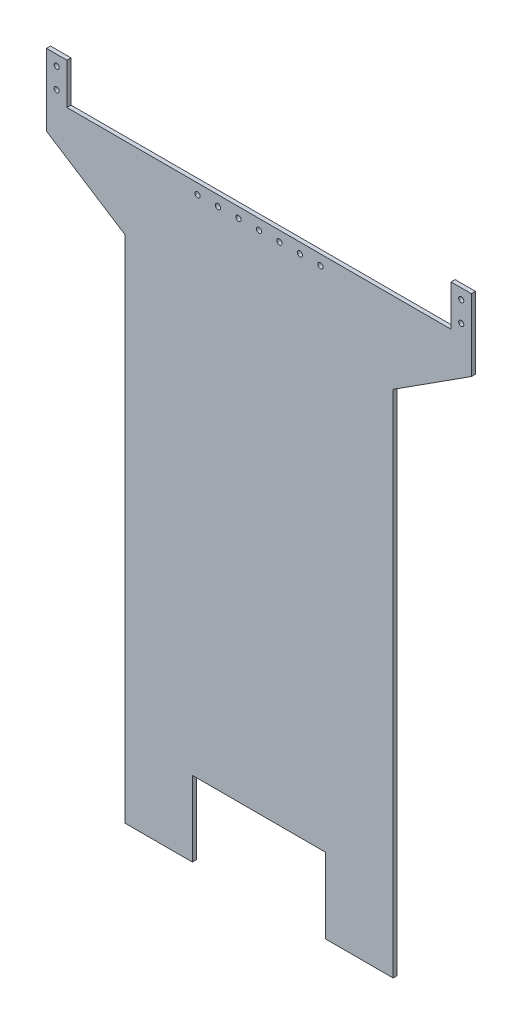
SolidWorks part; units mm, degrees
ref_plane "Front Plane" through (0, 0, 0) normal (0, 0, 1) x (1, 0, 0)
ref_plane "Top Plane" through (0, 0, 0) normal (0, 1, 0) x (1, 0, 0)
ref_plane "Right Plane" through (0, 0, 0) normal (1, 0, 0) x (0, 0, -1)
sketch "Sketch1" plane through (0, 0, 0) normal (0, 0, 1) x (1, 0, 0)
  line L9 (0, -55) -> (0, 55) construction
  line L16 (131, 509.412) -> (131, 0)
  line L17 (131, 0) -> (65, 0)
  line L18 (-131, 0) -> (-131, 509.412)
  line L22 (207.5, 558.4865) -> (207.5, 628.4865)
  line L34 (207.5, 628.4865) -> (187.5, 628.4865)
  line L35 (187.5, 628.4865) -> (187.5, 588.4865)
  line L37 (187.5, 588.4865) -> (-187.5, 588.4865)
  line L41 (-187.5, 588.4865) -> (-187.5, 628.4865)
  line L42 (-187.5, 628.4865) -> (-207.5, 628.4865)
  line L43 (-207.5, 628.4865) -> (-207.5, 558.4865)
  line L44 (207.5, 558.4865) -> (131, 509.412)
  line L45 (-207.5, 558.4865) -> (-131, 509.412)
  line L46 (65, 0) -> (65, 85)
  line L47 (65, 85) -> (-65, 85)
  line L48 (-65, 85) -> (-65, 0)
  line L49 (-65, 0) -> (-131, 0)
  circle A4 centre (197.5, 618.4865) radius 2.5
  circle A5 centre (197.5, 598.4865) radius 2.5
  circle A6 centre (-197.5, 598.4865) radius 2.5
  circle A7 centre (-197.5, 618.4865) radius 2.5
  point P8 (0, 85)
  point P16 (197.5, 628.4865)
  dimension "D5" = 588.4865
  dimension "D14" = 66
  dimension "D6" = 5
  dimension "D8" = 20
  dimension "D1" = 76.5
  dimension "D2" = 20
  dimension "D3" = 262
  dimension "D4" = 30
  dimension "D7" = 10
  dimension "D9" = 40
  dimension "D10" = 32.68
  dimension "D11" = 130
  dimension "D13" = 85
  dimension "D12" = 85
extrude "Boss-Extrude1" add sketch "Sketch1" against normal blind 4
sketch "Sketch4" plane through (0, 0, -4) normal (0, 0, -1) x (-1, 0, 0)
  line L0 (-187.5, 588.4865) -> (187.5, 588.4865) construction
  circle A0 centre (0, 578.4865) radius 2.55
  circle A1 centre (20, 578.4865) radius 2.55
  circle A2 centre (40, 578.4865) radius 2.55
  circle A3 centre (60, 578.4865) radius 2.55
  circle A4 centre (0, 578.4865) radius 2.55
  circle A5 centre (20, 578.4865) radius 2.55
  circle A6 centre (40, 578.4865) radius 2.55
  circle A7 centre (-20, 578.4865) radius 2.55
  circle A8 centre (0, 578.4865) radius 2.55
  circle A9 centre (20, 578.4865) radius 2.55
  circle A10 centre (-40, 578.4865) radius 2.55
  circle A11 centre (-20, 578.4865) radius 2.55
  circle A12 centre (0, 578.4865) radius 2.55
  circle A13 centre (-20, 578.4865) radius 2.55
  circle A14 centre (-40, 578.4865) radius 2.55
  circle A15 centre (-60, 578.4865) radius 2.55
  point P4 (0, 588.4865)
  dimension "D1" = 5.1
  dimension "D7" = 10
  dimension "D2" = 10
  dimension "D4" = 20
  dimension "D5" = 20
  dimension "D6" = 4
  dimension "D3" = 4
extrude "Cut-Extrude1" cut sketch "Sketch4" against normal through all contours A15 | A10 | A0 | A7 | A1 | A2 | A3
sketch "Sketch6" plane through (0, 0, -4) normal (0, 0, -1) x (-1, 0, 0)
  line L0 (65, 8.48) -> (131, 8.48)
  line L1 (65, 0) -> (65, 85) construction
  line L2 (131, 509.412) -> (131, 0) construction
  line L3 (65, 8.48) -> (65, 0)
  line L4 (65, 0) -> (131, 0)
  line L5 (131, 0) -> (131, 8.48)
  line L6 (0, 55) -> (0, -55) construction
  line L7 (-131, 0) -> (-131, 8.48)
  line L8 (-65, 8.48) -> (-131, 8.48)
  line L9 (-65, 8.48) -> (-65, 0)
  line L10 (-65, 0) -> (-131, 0)
  dimension "D1" = 8.48
extrude "Cut-Extrude2" cut sketch "Sketch6" against normal through all
sketch "Sketch7" plane through (0, 0, -4) normal (0, 0, -1) x (-1, 0, 0)
  line L0 (-65, 11.655) -> (-131, 11.655)
  line L1 (-65, 85) -> (-65, 8.48) construction
  line L2 (-131, 8.48) -> (-131, 509.412) construction
  line L3 (-131, 11.655) -> (-131, 8.48)
  line L4 (-65, 11.655) -> (-65, 8.48)
  line L5 (-65, 8.48) -> (-131, 8.48)
  line L6 (0, 55) -> (0, -55) construction
  line L7 (65, 11.655) -> (65, 8.48)
  line L8 (65, 8.48) -> (131, 8.48)
  line L9 (131, 11.655) -> (131, 8.48)
  line L10 (65, 11.655) -> (131, 11.655)
  dimension "D1" = 3.175
extrude "Cut-Extrude3" cut sketch "Sketch7" against normal through all
